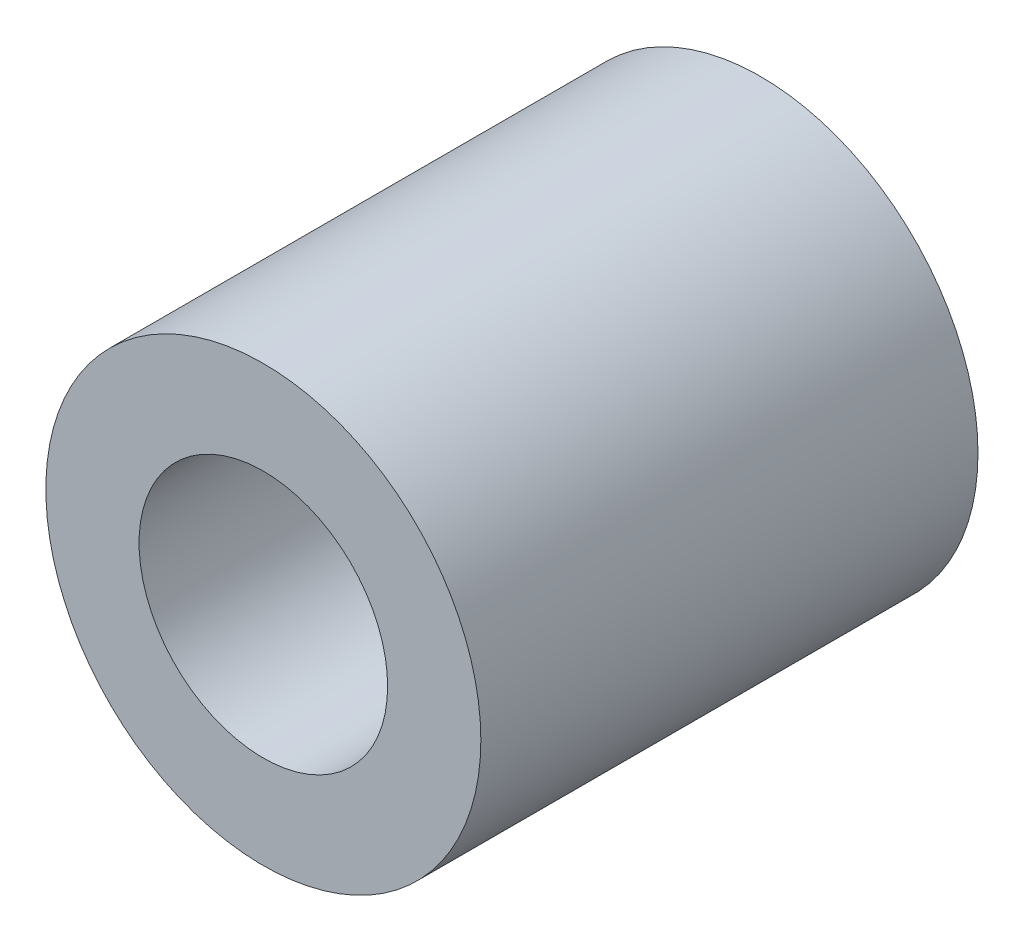
SolidWorks part; units mm, degrees
ref_plane "Front Plane" through (0, 0, 0) normal (0, 0, 1) x (1, 0, 0)
ref_plane "Top Plane" through (0, 0, 0) normal (0, 1, 0) x (1, 0, 0)
ref_plane "Right Plane" through (0, 0, 0) normal (1, 0, 0) x (0, 0, -1)
sketch "Sketch1" plane through (0, 0, 0) normal (0, 0, 1) x (1, 0, 0)
  circle A0 centre (0, 0) radius 4
  circle A1 centre (0, 0) radius 7
extrude "Boss-Extrude1" add sketch "Sketch1" along normal blind 16
